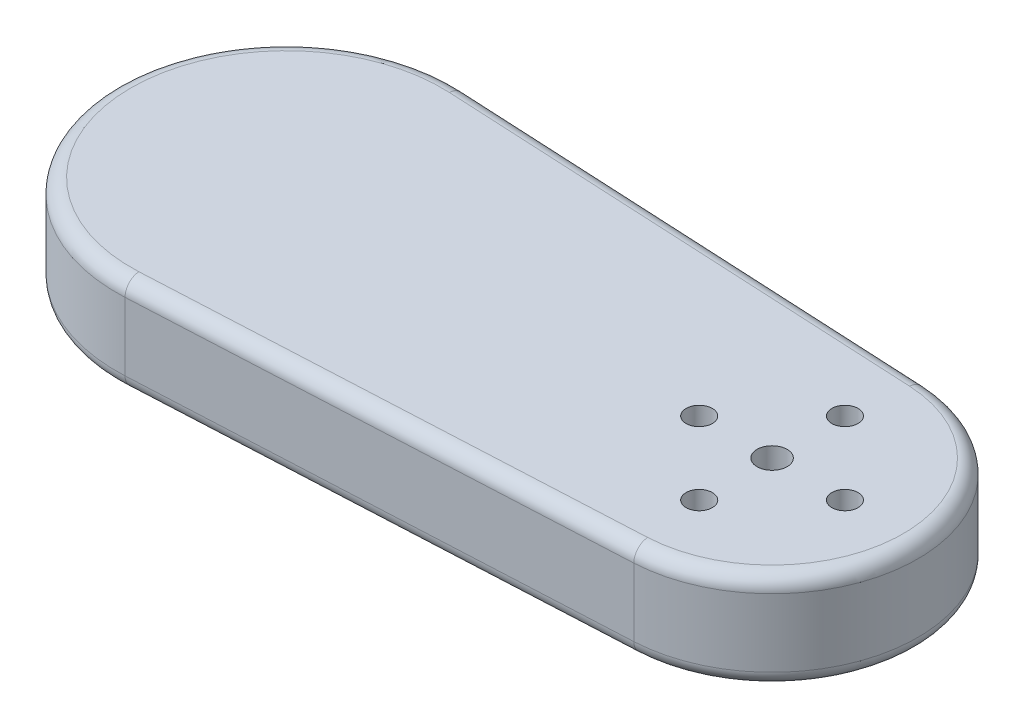
SolidWorks part; units mm, degrees
ref_plane "Front Plane" through (0, 0, 0) normal (0, 0, 1) x (1, 0, 0)
ref_plane "Top Plane" through (0, 0, 0) normal (0, 1, 0) x (1, 0, 0)
ref_plane "Right Plane" through (0, 0, 0) normal (1, 0, 0) x (0, 0, -1)
sketch "Sketch1" plane through (0, 0, 0) normal (0, 1, 0) x (1, 0, 0)
  line L0 (0, 0) -> (50, 0) construction
  line L1 (50.75, 14.9812) -> (0.875, 17.4781)
  line L2 (50.75, -14.9812) -> (0.875, -17.4781)
  circle A0 centre (0, 0) radius 14.5
  circle A1 centre (0, 0) radius 17.5
  circle A2 centre (50, 0) radius 15
  circle A3 centre (50, 0) radius 1.55
  circle A4 centre (57.5, 0) radius 1.35
  circle A5 centre (50, -7.5) radius 1.35
  circle A6 centre (50, 7.5) radius 1.35
  circle A7 centre (42.5, 0) radius 1.35
  dimension "D1" = 29
  dimension "D2" = 35
  dimension "D4" = 30
  dimension "D5" = 3.1
  dimension "D10" = 2.7
  dimension "D11" = 2.7
  dimension "D12" = 2.7
  dimension "D13" = 2.7
  dimension "D3" = 50
  dimension "D6" = 7.5
  dimension "D7" = 7.5
  dimension "D8" = 7.5
  dimension "D9" = 7.5
extrude "Boss-Extrude1" add sketch "Sketch1" along normal blind 10 contours L0 A1 L2 A2 | A1 L0 A2 L1 | A2 | A0 A1 region at (12.3213, 0, 11.7199) region at (26.0414, 0, -9.3866) region at (26.0414, 0, 9.3866) region at (39.9544, 0, -10.5611)
sketch "Sketch2" plane through (0, 10, 0) normal (0, 1, 0) x (1, 0, 0)
  circle A0 centre (0, 0) radius 14.5
  dimension "D1" = 29
extrude "Boss-Extrude2" add sketch "Sketch2" against normal blind 2.1
fillet "Fillet1" radius 1.5 9 edges at (65, 10, 0) (25.8125, 10, 16.2297) (-17.5, 10, 0) (25.8125, 10, -16.2297) (0, 0, 14.5) (65, 0, 0) (25.8125, 0, 16.2297) (-17.5, 0, 0) (25.8125, 0, -16.2297)
